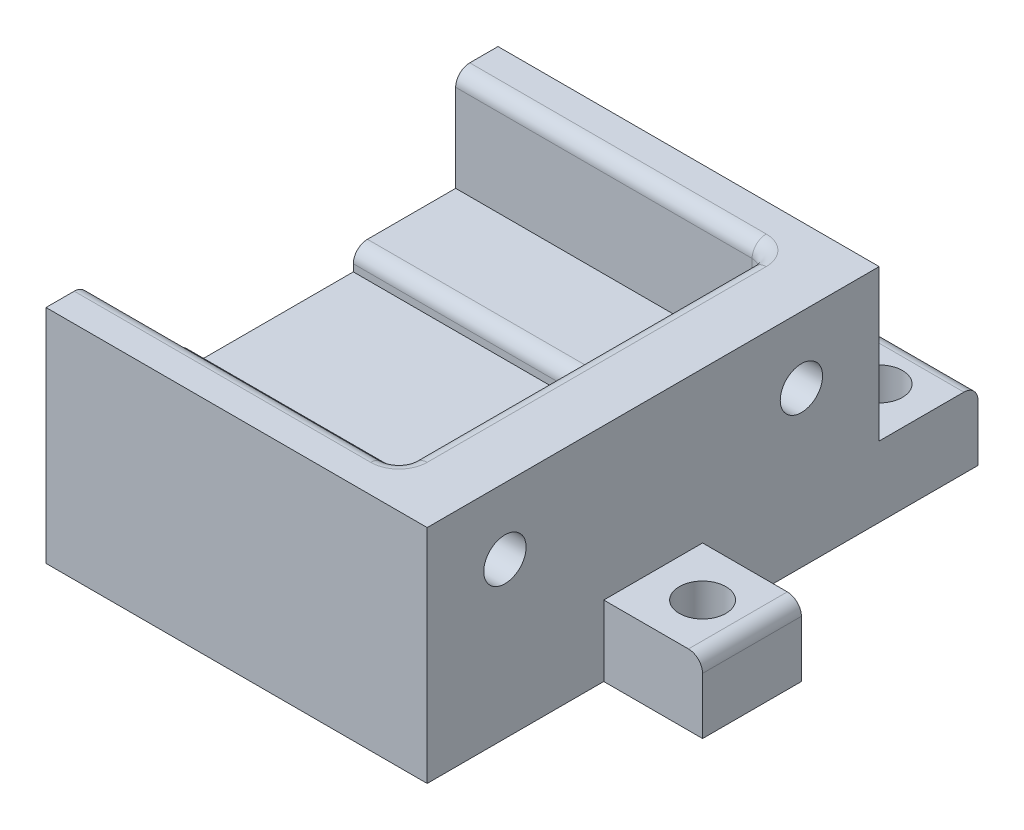
SolidWorks part; units mm, degrees
ref_plane "Front" through (0, 0, 0) normal (0, 0, 1) x (1, 0, 0)
ref_plane "Top" through (0, 0, 0) normal (0, 1, 0) x (1, 0, 0)
ref_plane "Right" through (0, 0, 0) normal (1, 0, 0) x (0, 0, -1)
sketch "Sketch1" plane through (0, 0, 0) normal (1, 0, 0) x (0, 0, -1)
  line L0 (-13.0089, 0) -> (13.0089, 0)
  line L1 (13.0089, 0) -> (13.0089, 8.5)
  line L2 (13.0089, 8.5) -> (5.7589, 8.5)
  line L3 (5.7589, 8.5) -> (5.7589, 7)
  line L4 (5.7589, 7) -> (-5.7589, 7)
  line L5 (-5.7589, 7) -> (-5.7589, 8.5)
  line L6 (-5.7589, 8.5) -> (-13.0089, 8.5)
  line L7 (-13.0089, 8.5) -> (-13.0089, 0)
  dimension "D1" = 8.5
  dimension "D2" = 7.25
  dimension "D3" = 26.0178
  dimension "D4" = 1.5
extrude "Boss-Extrude1" add sketch "Sketch1" along normal mid plane 22
sketch "Sketch3" plane through (0, 0, 0) normal (0, -1, 0) x (1, 0, 0)
  line L1 (-11, -13.0089) -> (11, -13.0089)
  line L2 (-11, -13.0089) -> (-11, -16.0089)
  line L3 (-11, -16.0089) -> (11, -16.0089)
  line L4 (11, -13.0089) -> (11, -16.0089)
  line L5 (-11, 13.0089) -> (11, 13.0089)
  line L6 (-11, 13.0089) -> (-11, 16.0089)
  line L7 (-11, 16.0089) -> (11, 16.0089)
  line L8 (11, 13.0089) -> (11, 16.0089)
  dimension "D1" = 3
  dimension "D2" = 22
  dimension "D3" = 3
  dimension "D4" = 22
extrude "Boss-Extrude2" add sketch "Sketch3" against normal blind 15.7
sketch "Sketch4" plane through (11, 0, 0) normal (1, 0, 0) x (0, 0, -1)
  line L0 (0, 0) -> (0, 15.7) construction
  line L1 (-16.0089, 0) -> (16.0089, 0) construction
  line L2 (-8.8, 15.7) -> (-16.0089, 15.7)
  line L3 (-16.0089, 15.7) -> (-16.0089, 0) construction
  line L4 (-16.0089, 15.7) -> (-16.0089, 0)
  line L5 (-16.0089, 0) -> (16.0089, 0)
  line L6 (16.0089, 0) -> (16.0089, 15.7)
  line L7 (16.0089, 15.7) -> (16.0089, 0) construction
  line L8 (16.0089, 15.7) -> (-8.8, 15.7)
  point P6 (0, 0)
  dimension "D2" = 15.7
extrude "Boss-Extrude3" add sketch "Sketch4" along normal blind 5
sketch "Sketch5" plane through (16, 0, 0) normal (1, 0, 0) x (0, 0, -1)
  line L0 (-16.0089, 11) -> (-10.5, 11) construction
  line L1 (-16.0089, 15.7) -> (-16.0089, 0) construction
  line L2 (-10.5, 11) -> (-10.5, 0) construction
  line L3 (-16.0089, 0) -> (16.0089, 0) construction
  line L4 (0, 0) -> (0, 15.7) construction
  line L5 (16.0089, 15.7) -> (-16.0089, 15.7) construction
  circle A0 centre (-10.5, 11) radius 1.5
  circle A1 centre (10.5, 11) radius 1.5
  point P13 (0, 0)
  dimension "D3" = 3
  dimension "D1" = 5.5089
  dimension "D2" = 11
extrude "Cut-Extrude1" cut sketch "Sketch5" against normal through all
sketch "Sketch6" plane through (0, 0, 0) normal (0, -1, 0) x (1, 0, 0)
  line L0 (16, 16.0089) -> (16, -16.0089) construction
  line L5 (0, 0) -> (16, 0) construction
  line L13 (16, 3.5) -> (23, 3.5)
  line L14 (-11, -16.0089) -> (16, -16.0089) construction
  line L15 (16, -23.0089) -> (9, -23.0089)
  line L20 (16, -23.0089) -> (16, -16.0089)
  line L21 (16, -16.0089) -> (9, -16.0089)
  line L22 (9, -23.0089) -> (9, -16.0089)
  line L23 (16, 3.5) -> (16, -3.5)
  line L24 (16, -3.5) -> (23, -3.5)
  line L25 (23, 3.5) -> (23, -3.5)
  dimension "D1" = 7
  dimension "D2" = 7
  dimension "D3" = 7
  dimension "D4" = 7
extrude "Boss-Extrude4" add sketch "Sketch6" against normal blind 5
sketch "Sketch7" plane through (0, 5, 0) normal (0, 1, 0) x (1, 0, 0)
  line L0 (23, 0) -> (16, 0) construction
  line L1 (9, 23.0089) -> (16, 23.0089) construction
  line L2 (16, 16.0089) -> (9, 16.0089) construction
  line L3 (19.5, 3.5) -> (19.5, -3.5) construction
  line L6 (12.5, 23.0089) -> (12.5, 16.0089) construction
  line L7 (16, -3.5) -> (16, 3.5) construction
  line L8 (23, 3.5) -> (23, -3.5) construction
  line L9 (9, 19.5089) -> (16, 19.5089) construction
  line L10 (16, 3.5) -> (23, 3.5) construction
  line L11 (23, -3.5) -> (16, -3.5) construction
  line L12 (9, 16.0089) -> (9, 23.0089) construction
  line L15 (16, 23.0089) -> (16, 16.0089) construction
  circle A0 centre (19.5, 0) radius 1.65
  circle A1 centre (12.5, 19.5089) radius 1.65
  point P5 (16, 0)
  point P11 (23, 0)
  point P29 (19.5, 3.5)
  dimension "D1" = 3.3
extrude "Cut-Extrude2" cut sketch "Sketch7" against normal through all
fillet "Fillet1" radius 1 9 edges at (0, 8.5, 5.7589) (0, 8.5, -5.7589) (23, 5, 0) (12.5, 5, -23.0089) (0, 15.7, 13.0089) (11, 15.7, 0) (0, 15.7, -13.0089) (11, 12.1, 13.0089) (11, 12.1, -13.0089)
